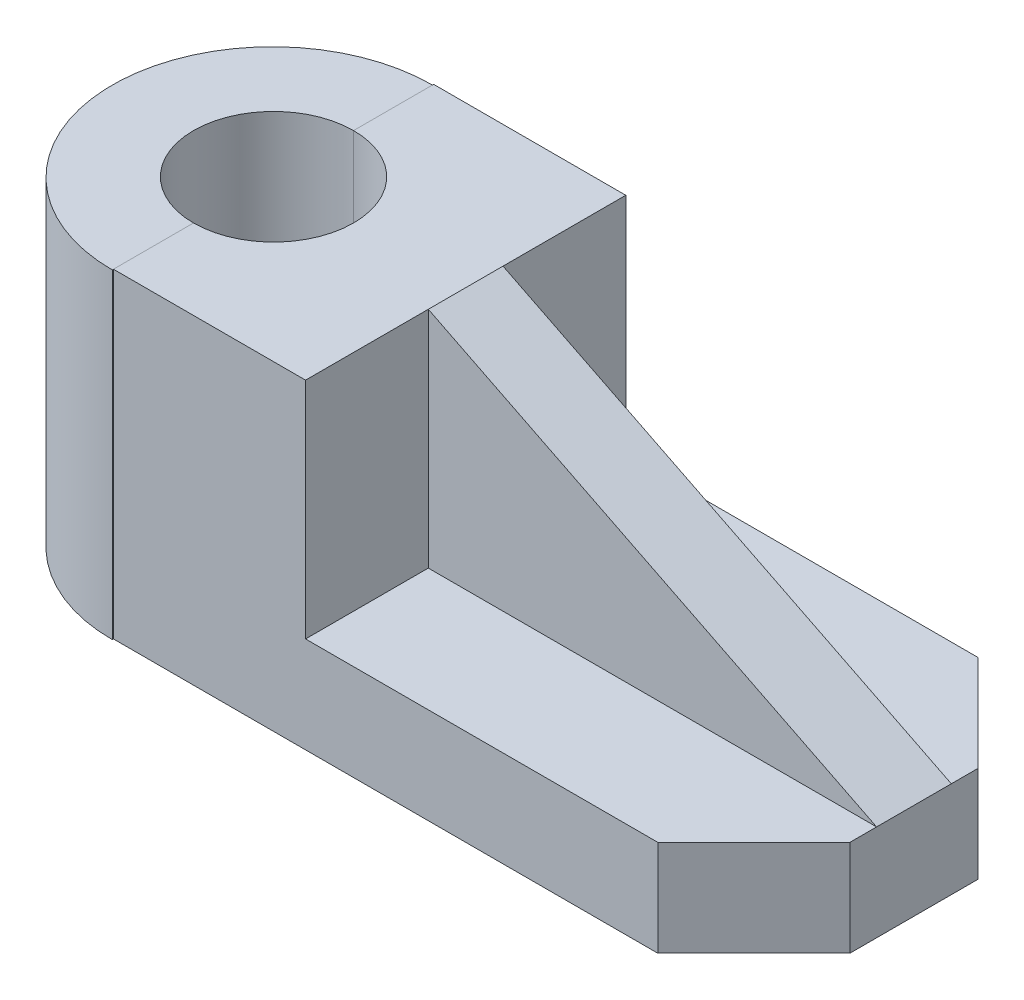
SolidWorks part; units mm, degrees
ref_plane "Front Plane" through (0, 0, 0) normal (0, 0, 1) x (1, 0, 0)
ref_plane "Top Plane" through (0, 0, 0) normal (0, 1, 0) x (1, 0, 0)
ref_plane "Right Plane" through (0, 0, 0) normal (1, 0, 0) x (0, 0, -1)
sketch "Sketch1" plane through (0, 0, 0) normal (0, 0, 1) x (1, 0, 0)
  line L0 (-18, 30) -> (0, 30)
  line L1 (0, 30) -> (0, 9)
  line L2 (0, 9) -> (42, 9)
  line L3 (42, 9) -> (42, 0)
  line L4 (42, 0) -> (0, 0)
  line L5 (0, 0) -> (-18, 0)
  line L6 (-18, 0) -> (-18, 30)
  dimension "D1" = 18
  dimension "D2" = 60
  dimension "D3" = 30
  dimension "D4" = 9
extrude "Boss-Extrude1" add sketch "Sketch1" against normal blind 15 and the other way blind 15
sketch "Sketch2" plane through (0, 30, 0) normal (0, 1, 0) x (1, 0, 0)
  line L0 (-18, 15) -> (-18, -15) construction
  line L1 (-18, 14.8899) -> (-18, -15.1101)
  arc A0 (-18, 14.8899) -> (-18, -15.1101) centre (-18, -0.1101) ccw
  point P3 (0, 0)
  point P6 (-18, -0.1101)
  dimension "D2" = 15
  dimension "D1" = 30
extrude "Boss-Extrude2" add sketch "Sketch2" against normal blind 30
sketch "Sketch3" plane through (0, 30, 0) normal (0, 1, 0) x (1, 0, 0)
  line L0 (0, 15) -> (-18, 15) construction
  line L1 (0, 15) -> (0, -15) construction
  circle A0 centre (-18, 0) radius 7.5
  circle A1 centre (-18, 0) radius 7.5
  dimension "D1" = 15
  dimension "D2" = 15
  dimension "D3" = 18
chamfer "Chamfer1" distance 9 angle 45 1 edges at (42, 4.5, 15)
chamfer "Chamfer2" distance 9 angle 45 1 edges at (42, 4.5, -15)
extrude "Cut-Extrude2" cut sketch "Sketch3" against normal through all contours A0
sketch "Sketch16" plane through (0, 0, 0) normal (0, 0, 1) x (1, 0, 0)
  line L0 (0, 30) -> (42, 9)
rib "Rib14" sketch "Sketch16" sketch "Sketch16" thickness 7 extrusion direction parallel to sketch draft on no parameters "D1"=7
